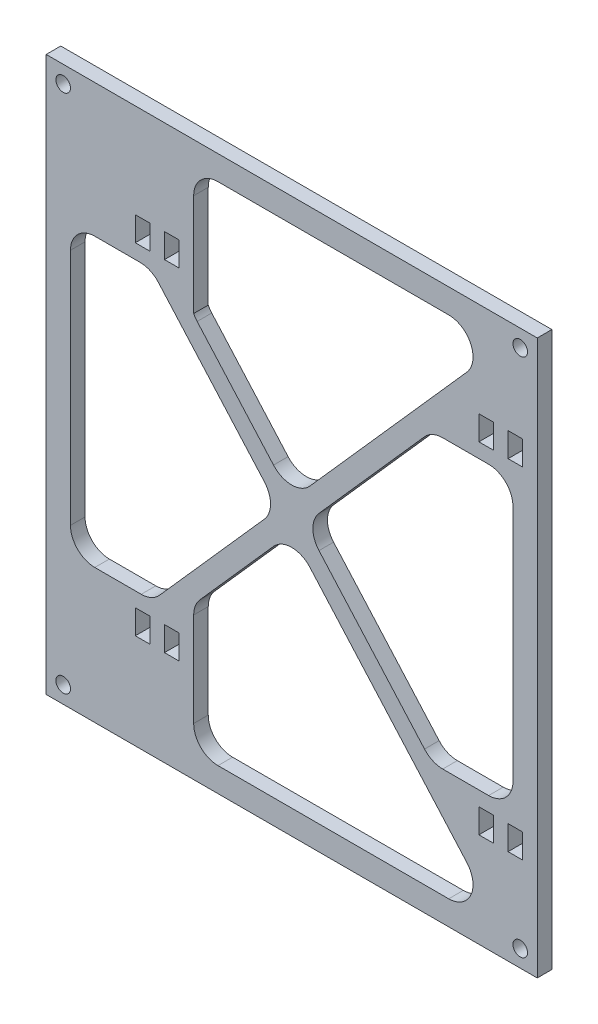
SolidWorks part; units mm, degrees
ref_plane "Front Plane" through (0, 0, 0) normal (0, 0, 1) x (1, 0, 0)
ref_plane "Top Plane" through (0, 0, 0) normal (0, 1, 0) x (1, 0, 0)
ref_plane "Right Plane" through (0, 0, 0) normal (1, 0, 0) x (0, 0, -1)
sketch "Sketch1" plane through (0, 0, 0) normal (0, 0, 1) x (1, 0, 0)
  line L0 (71.6864, -54.1061) -> (71.6572, -54.0732)
  line L1 (71.6864, 56.8779) -> (-29.3136, 56.8779)
  line L2 (71.6864, 56.8779) -> (71.6864, -57.1221)
  line L3 (71.6864, -57.1221) -> (-29.3136, -57.1221)
  line L4 (-29.3136, 56.8779) -> (-29.3136, -57.1221)
  line L5 (71.6864, 56.8779) -> (-29.3136, -57.1221) construction
  line L6 (71.6864, -57.1221) -> (-29.3136, 56.8779) construction
  line L7 (-11.1018, -52.1221) -> (53.4747, -52.1221)
  line L8 (-24.3136, -35.2791) -> (-24.3136, 35.035)
  line L9 (-11.1018, 51.8779) -> (53.4747, 51.8779)
  line L10 (66.6864, -35.2791) -> (66.6864, 35.035)
  line L11 (-23.7247, -50.8138) -> (66.0975, 50.5697) construction
  line L12 (-23.7247, 50.5697) -> (66.0975, -50.8138) construction
  line L13 (69.0144, 56.8779) -> (68.9414, 56.7956)
  line L14 (69.0144, -57.1221) -> (68.9414, -57.0397)
  line L15 (71.6864, 53.862) -> (71.6572, 53.829)
  line L16 (73.1834, 55.5517) -> (-27.8166, -58.4483) construction
  line L17 (70.1894, 58.2042) -> (-30.8106, -55.7958) construction
  line L18 (57.9439, 38.3507) -> (26.796, 3.1936)
  line L19 (57.2172, 43.5622) -> (24.9289, 7.1181)
  line L20 (17.4439, -7.3622) -> (-14.8443, -43.8064)
  line L21 (17.4439, 7.1181) -> (-14.8443, 43.5622)
  line L22 (73.1834, -55.7958) -> (-27.8166, 58.2042) construction
  line L23 (15.5768, -3.4378) -> (-15.5711, -38.5948)
  line L24 (15.5768, 3.1936) -> (-15.5711, 38.3507)
  line L25 (70.1894, -58.4483) -> (-30.8106, 55.5517) construction
  line L26 (57.9439, -38.5948) -> (26.796, -3.4378)
  line L27 (57.2172, -43.8064) -> (24.9289, -7.3622)
  line L28 (-26.5685, -57.0397) -> (-26.6415, -57.1221)
  line L29 (-29.2844, -54.0732) -> (-29.3136, -54.1061)
  circle A0 centre (68.1864, 53.3779) radius 1.5
  circle A1 centre (68.1864, -53.6221) radius 1.5
  circle A2 centre (-25.8136, -53.6221) radius 1.5
  circle A3 centre (-25.8136, 53.3779) radius 1.5
  circle A4 centre (-25.8136, 53.3779) radius 3.5 construction
  circle A5 centre (-25.8136, -53.6221) radius 3.5 construction
  circle A6 centre (68.1864, -53.6221) radius 3.5 construction
  circle A7 centre (68.1864, 53.3779) radius 3.5 construction
  arc A9 (15.5768, 3.1936) -> (15.5768, -3.4378) centre (11.8343, -0.1221) cw
  arc A10 (17.4439, -7.3622) -> (24.9289, -7.3622) centre (21.1864, -10.6779) cw
  arc A11 (26.796, -3.4378) -> (26.796, 3.1936) centre (30.5385, -0.1221) cw
  arc A12 (24.9289, 7.1181) -> (17.4439, 7.1181) centre (21.1864, 10.4338) cw
  arc A13 (-11.1018, 51.8779) -> (-14.8443, 43.5622) centre (-11.1018, 46.8779) ccw
  arc A14 (-15.5711, 38.3507) -> (-24.3136, 35.035) centre (-19.3136, 35.035) ccw
  arc A15 (-15.5711, -38.5948) -> (-24.3136, -35.2791) centre (-19.3136, -35.2791) cw
  arc A16 (-14.8443, -43.8064) -> (-11.1018, -52.1221) centre (-11.1018, -47.1221) ccw
  arc A17 (57.2172, -43.8064) -> (53.4747, -52.1221) centre (53.4747, -47.1221) cw
  arc A18 (66.6864, -35.2791) -> (57.9439, -38.5948) centre (61.6864, -35.2791) cw
  arc A19 (66.6864, 35.035) -> (57.9439, 38.3507) centre (61.6864, 35.035) ccw
  arc A20 (57.2172, 43.5622) -> (53.4747, 51.8779) centre (53.4747, 46.8779) ccw
  point P0 (21.1864, -0.1221)
  point P6 (21.1864, -0.1221)
  point P67 (18.5144, -0.1221)
  point P84 (64.5846, -52.1221)
  point P87 (66.6864, -48.4625)
  dimension "D4" = 5
  dimension "D1" = 2
  dimension "D2" = 2
  dimension "D3" = 2
extrude "Boss-Extrude1" add sketch "Sketch1" along normal blind 3 contours L1 L4 L3 L2 A20 L19 A12 L21 A13 L9 A19 L10 A18 L26 A11 L18 L23 A15 L8 A14 L24 A9 A3 A2 A1 A0 region at (21.1864, -0.1221, 0)
sketch "Sketch2" plane through (0, 0, 3) normal (0, 0, 1) x (1, 0, 0)
  line L0 (66.6864, -35.2791) -> (66.6864, 35.035) construction
  line L1 (65.6864, 37.3779) -> (68.6864, 37.3779)
  line L2 (65.6864, 37.3779) -> (65.6864, 32.3779)
  line L3 (65.6864, 32.3779) -> (68.6864, 32.3779)
  line L4 (68.6864, 37.3779) -> (68.6864, 32.3779)
  line L5 (70.0993, 29.3779) -> (49.9944, 29.3779)
  line L6 (57.9439, 38.3507) -> (26.796, 3.1936) construction
  line L7 (69.75, -29.6221) -> (49.9944, -29.6221)
  line L8 (57.9439, -38.5948) -> (26.796, -3.4378) construction
  line L9 (71.6864, 56.8779) -> (71.6864, -57.1221) construction
  line L10 (59.6864, 37.3779) -> (62.6864, 37.3779)
  line L11 (59.6864, 37.3779) -> (59.6864, 32.3779)
  line L12 (62.6864, 37.3779) -> (62.6864, 32.3779)
  line L13 (59.6864, 32.3779) -> (62.6864, 32.3779)
  line L14 (65.6864, -32.6221) -> (68.6864, -32.6221)
  line L15 (65.6864, -32.6221) -> (65.6864, -37.6221)
  line L16 (65.6864, -37.6221) -> (68.6864, -37.6221)
  line L17 (68.6864, -32.6221) -> (68.6864, -37.6221)
  line L18 (59.6864, -32.6221) -> (62.6864, -32.6221)
  line L19 (59.6864, -32.6221) -> (59.6864, -37.6221)
  line L20 (62.6864, -32.6221) -> (62.6864, -37.6221)
  line L21 (59.6864, -37.6221) -> (62.6864, -37.6221)
  line L22 (61.1864, 32.3779) -> (61.1864, -32.6221) construction
  line L23 (66.6864, -0.1221) -> (61.1864, -0.1221) construction
  line L24 (49.9944, -29.6221) -> (69.75, -51.9204)
  line L25 (69.75, -51.9204) -> (69.75, -29.6221)
  line L26 (49.9944, 29.3779) -> (70.0993, 52.7452)
  line L27 (70.0993, 52.7452) -> (70.0993, 29.3779)
  arc A0 (57.9439, -38.5948) -> (66.6864, -35.2791) centre (61.6864, -35.2791) ccw construction
  arc M27 (57.9439, 38.3507) -> (66.6864, 35.035) centre (61.6864, 35.035) cw
  line M28 (66.6864, 35.035) -> (66.6864, -35.2791)
  dimension "D1" = 3
  dimension "D2" = 5
  dimension "D3" = 3
  dimension "D6" = 65
  dimension "D7" = 3
  dimension "D8" = 3
  dimension "D9" = 3
  dimension "D4" = 2
  dimension "D5" = 2
extrude "Boss-Extrude2" add sketch "Sketch2" against normal blind 3
extrude "Cut-Extrude1" cut sketch "Sketch2<2>" against normal blind 3 contours L4 L1 L3 M27 M28 | L17 L16 L15 L14 region at (67.6365, 34.9596, 3)
sketch "Sketch2<2>" plane through (0, 0, 3) normal (0, 0, 1) x (1, 0, 0) same geometry as "Sketch2"
sketch "Sketch3" plane through (0, 0, 3) normal (0, 0, 1) x (1, 0, 0)
  line L0 (-10.9777, -32.5) -> (-7.9777, -32.5)
  line L1 (17.4439, -7.3622) -> (-14.8443, -43.8064) construction
  line L9 (-10.9777, -32.5) -> (-10.9777, -37.5)
  line L10 (-10.9777, -37.5) -> (-7.9777, -37.5)
  line L11 (-7.9777, -32.5) -> (-7.9777, -37.5)
  line L12 (-4.9777, -32.5) -> (-1.9777, -32.5)
  line L13 (-4.9777, -32.5) -> (-4.9777, -37.5)
  line L14 (-4.9777, -37.5) -> (-1.9777, -37.5)
  line L15 (-1.9777, -32.5) -> (-1.9777, -37.5)
  line L17 (-1.9777, -37.5) -> (-1.9777, -32.5) construction
  line L18 (1.0223, -25.8975) -> (1.0223, -52.1221)
  line L20 (-11.1018, -52.1221) -> (53.4747, -52.1221) construction
  line L21 (-7.5134, -29.5) -> (-24.3136, -29.5)
  line L22 (15.5768, -3.4378) -> (-15.5711, -38.5948) construction
  line L23 (-24.3136, -35.2791) -> (-24.3136, 35.035) construction
  line L24 (1.0223, -25.8975) -> (-7.5134, -29.5)
  line L25 (-24.3136, -29.5) -> (-24.3136, -52.1221)
  line L26 (-24.3136, -52.1221) -> (1.0223, -52.1221)
  dimension "D1" = 32.5
  dimension "D2" = 3
  dimension "D3" = 5
  dimension "D6" = 3
  dimension "D7" = 3
  dimension "D4" = 3
extrude "Boss-Extrude3" add sketch "Sketch3" against normal blind 3
extrude "Cut-Extrude2" cut sketch "Sketch3<2>" against normal blind 3 contours L11 L10 L9 L0 | L13 L14 L15 L12
sketch "Sketch3<2>" plane through (0, 0, 3) normal (0, 0, 1) x (1, 0, 0) same geometry as "Sketch3"
mirror "Mirror1" about plane through (0, 0, 0) normal (0, 1, 0) of "Boss-Extrude3", "Cut-Extrude2"
fillet "Fillet4" radius 5 12 edges at (-7.5134, -29.5, 1.5) (-24.3136, -29.5, 1.5) (1.0223, -52.1221, 1.5) (1.0223, -25.8975, 1.5) (1.0223, 51.8779, 1.5) (-24.3136, 29.5, 1.5) (-7.7297, 29.5, 1.5) (49.9944, 29.3779, 1.5) (66.6864, 29.3779, 1.5) (66.6864, -29.6221, 1.5) (49.9944, -29.6221, 1.5) (0.6768, 26.0433, 1.5)
